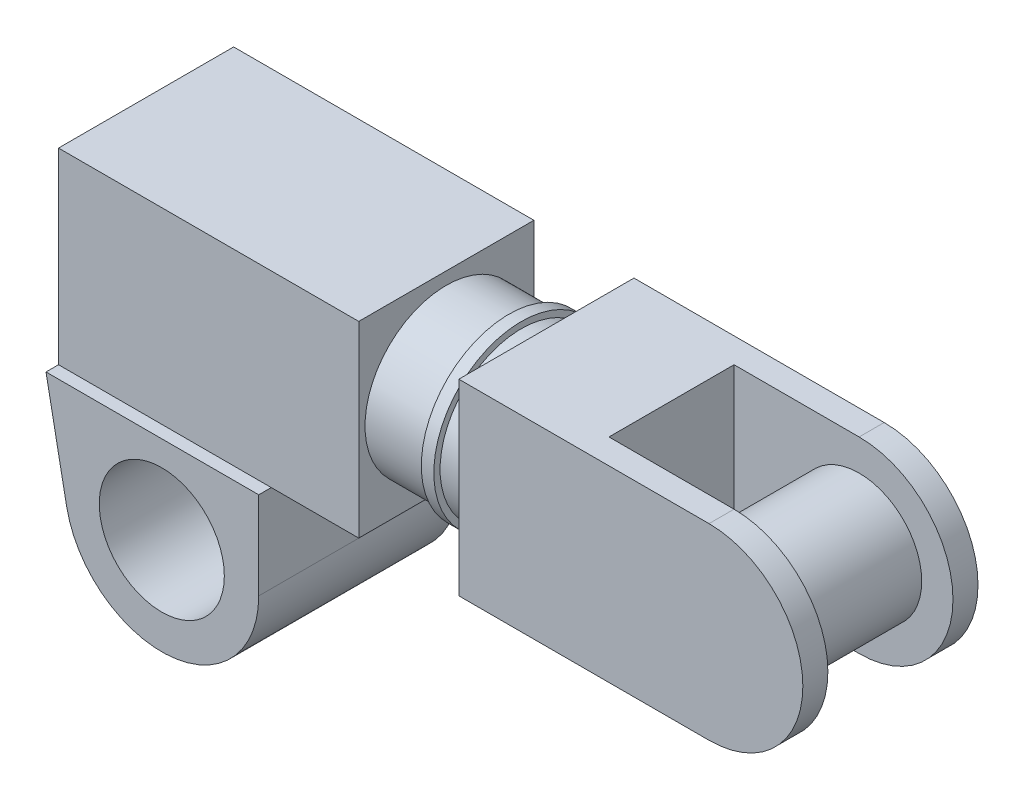
SolidWorks part; units mm, degrees
ref_plane "Front Plane" through (0, 0, 0) normal (0, 0, 1) x (1, 0, 0)
ref_plane "Top Plane" through (0, 0, 0) normal (0, 1, 0) x (1, 0, 0)
ref_plane "Right Plane" through (0, 0, 0) normal (1, 0, 0) x (0, 0, -1)
sketch "Sketch1" plane through (0, 0, 0) normal (1, 0, 0) x (0, 0, -1)
  line L1 (-70, 75) -> (70, 75)
  line L2 (-70, 75) -> (-70, -75)
  line L3 (-70, -75) -> (70, -75)
  line L4 (70, 75) -> (70, -75)
  line L5 (-70, 75) -> (70, -75) construction
  line L6 (-70, -75) -> (70, 75) construction
  point P0 (0, 0)
  dimension "D1" = 150
  dimension "D2" = 140
extrude "Boss-Extrude1" add sketch "Sketch1" along normal blind 240
sketch "Sketch2" plane through (240, 0, 0) normal (1, 0, 0) x (0, 0, -1)
  circle A0 centre (0, 0) radius 65
  dimension "D1" = 130
extrude "Boss-Extrude2" add sketch "Sketch2" along normal blind 50
sketch "Sketch3" plane through (290, 0, 0) normal (1, 0, 0) x (0, 0, -1)
  circle A0 centre (0, 0) radius 70
  dimension "D1" = 140
extrude "Boss-Extrude3" add sketch "Sketch3" along normal blind 10
sketch "Sketch4" plane through (0, 0, 0) normal (0, 0, 1) x (1, 0, 0)
  line L0 (0, -75) -> (16.4811, -159.7877)
  line L1 (0, 75) -> (0, -75) construction
  line L2 (170.0572, -75) -> (170.0572, -145)
  line L3 (240, -75) -> (0, -75) construction
  line L4 (0, -75) -> (170.0572, -75)
  arc A0 (16.4811, -159.7877) -> (170.0572, -145) centre (92.5572, -145) ccw
  circle A1 centre (92.5572, -145) radius 50
  dimension "D1" = 155
  dimension "D2" = 100
  dimension "D3" = 191
  dimension "D4" = 70
extrude "Boss-Extrude4" add sketch "Sketch4" along normal mid plane 160
sketch "Sketch5" plane through (300, 0, 0) normal (1, 0, 0) x (0, 0, -1)
  circle A0 centre (0, 0) radius 65
  dimension "D1" = 130
extrude "Boss-Extrude5" add sketch "Sketch5" along normal blind 20
sketch "Sketch6" plane through (0, 0, 0) normal (0, 0, 1) x (1, 0, 0)
  line L0 (520, 75) -> (320, 75)
  line L1 (320, 75) -> (320, -75)
  line L2 (320, -75) -> (520, -75)
  line L3 (320, -65) -> (320, 65) construction
  arc A0 (520, -75) -> (520, 75) centre (520, 0) ccw
  dimension "D1" = 150
  dimension "D2" = 200
extrude "Boss-Extrude6" add sketch "Sketch6" along normal mid plane 140
sketch "Sketch7" plane through (0, 0, 0) normal (0, 0, 1) x (1, 0, 0)
  line L0 (520, 75) -> (420, 75)
  line L1 (520, 75) -> (320, 75) construction
  line L2 (420, 75) -> (420, -75)
  line L3 (320, -75) -> (520, -75) construction
  line L4 (420, -75) -> (520, -75)
  arc A0 (520, -75) -> (520, 75) centre (520, 0) ccw construction
  arc A1 (520, -75) -> (520, 75) centre (520, 0) ccw
extrude "Cut-Extrude1" cut sketch "Sketch7" against normal mid plane 100
sketch "Sketch8" plane through (0, 0, -50) normal (0, 0, 1) x (1, 0, 0)
  circle A0 centre (520, 0) radius 50
  dimension "D1" = 100
extrude "Boss-Extrude7" add sketch "Sketch8" along normal up to next
split "Split1" bodies to split 108 resulting bodies 109 110 split by face at (240, 0, -65)
